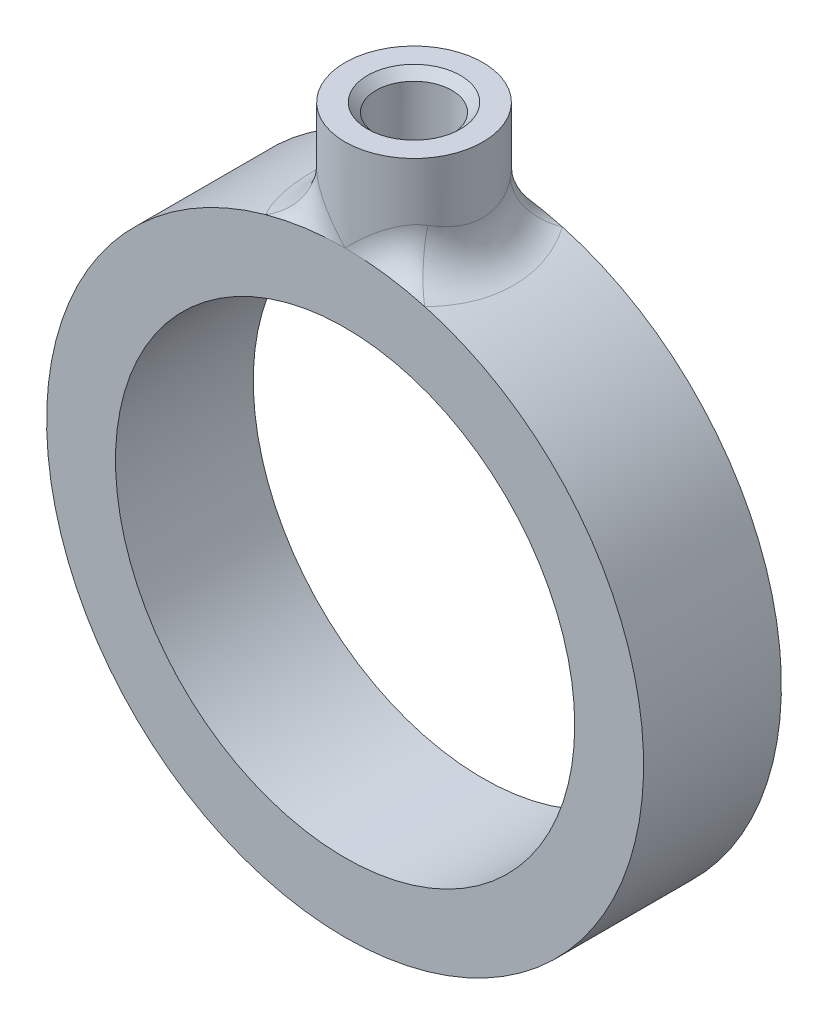
SolidWorks part; units mm, degrees
ref_plane "Front Plane" through (0, 0, 0) normal (0, 0, 1) x (1, 0, 0)
ref_plane "Top Plane" through (0, 0, 0) normal (0, 1, 0) x (1, 0, 0)
ref_plane "Right Plane" through (0, 0, 0) normal (1, 0, 0) x (0, 0, -1)
sketch "Sketch1" plane through (0, 0, 0) normal (0, 0, 1) x (1, 0, 0)
  circle A0 centre (0, 0) radius 13
  circle A1 centre (0, 0) radius 10
  dimension "D1" = 20
  dimension "D2" = 26
extrude "Boss-Extrude1" add sketch "Sketch1" along normal mid plane 6
sketch "Sketch2" plane through (0, 0, 0) normal (0, 1, 0) x (1, 0, 0)
  circle A0 centre (0, 0) radius 3
  dimension "D1" = 6
extrude "Boss-Extrude2" add sketch "Sketch2" against normal up to next from offset 17
fillet "Fillet1" radius 2 2 edges at (2.9196, 12.6679, 0.69) (-2.9196, 12.6679, 0.69)
hole_wizard "M4 Tapped Hole1" positions "Sketch3" profile "Sketch4" tap size "M4" standard "ISO"
sketch "Sketch3" plane through (0, 17, 0) normal (0, 1, 0) x (1, 0, 0)
  point P0 (0, 0)
sketch "Sketch4" plane through (0, 17, 0) normal (1, 0, 0) x (0, 0, 1)
  line L0 (0, 0) -> (0, 14.9914)
  line L1 (0, 14.9914) -> (1.65, 14)
  line L2 (1.65, 14) -> (1.65, 0.375)
  line L3 (1.65, 0.375) -> (2.025, 0)
  line L5 (2.025, 0) -> (0, 0)
  line L6 (-1.65, 0.375) -> (-2.025, 0) construction
  line L10 (0, 14.9914) -> (-1.65, 14) construction
  line L11 (0, -6.35) -> (0, 107.95) construction
  dimension "Tap Drill Dia." = 3.3
  dimension "Tap Drill Depth" = 14
  dimension "Near C'Sink Dia." = 4.05
  dimension "Near C'Sink Angle" = 90
  dimension "Drill Angle" = 118
cosmetic thread "Hole Thread1" parameters "D1"=7.1371, "D2"=4
